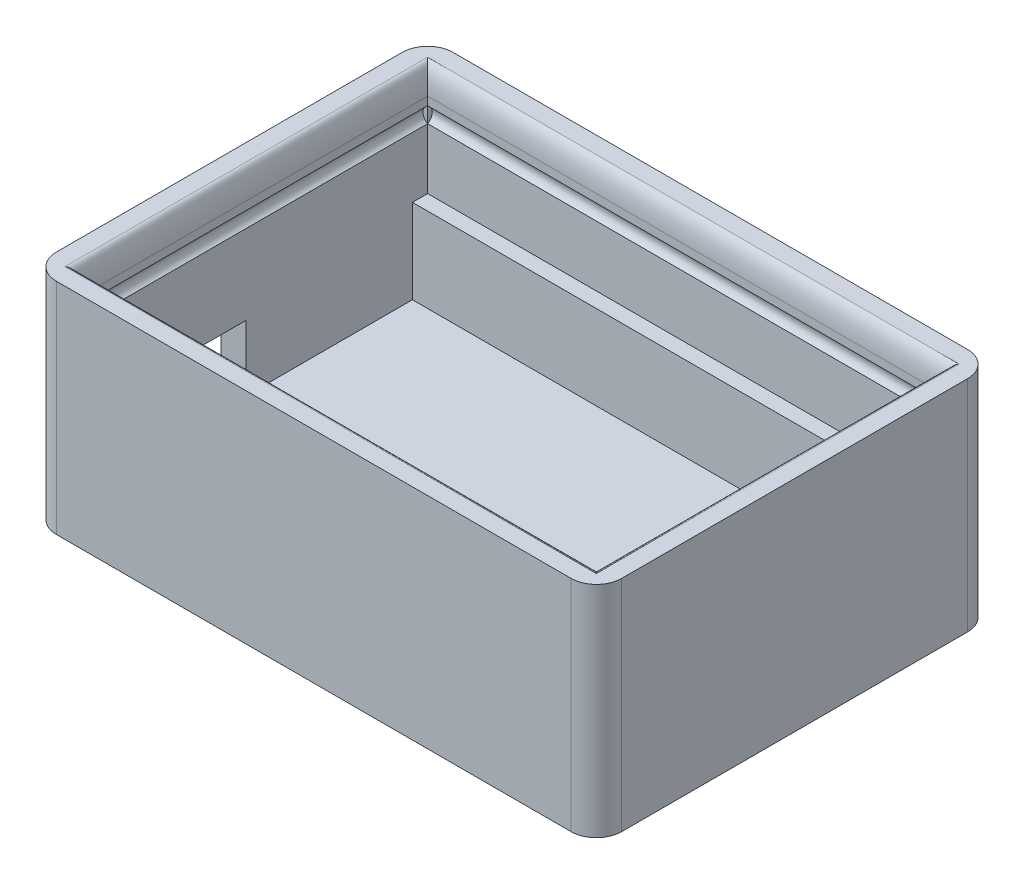
SolidWorks part; units mm, degrees
ref_plane "Front Plane" through (0, 0, 0) normal (0, 0, 1) x (1, 0, 0)
ref_plane "Top Plane" through (0, 0, 0) normal (0, 1, 0) x (1, 0, 0)
ref_plane "Right Plane" through (0, 0, 0) normal (1, 0, 0) x (0, 0, -1)
sketch "Sketch1" plane through (0, 0, 0) normal (0, 1, 0) x (1, 0, 0)
  line L1 (-30.5, 20.5) -> (30.5, 20.5)
  line L2 (-30.5, 20.5) -> (-30.5, -20.5)
  line L3 (-30.5, -20.5) -> (30.5, -20.5)
  line L4 (30.5, 20.5) -> (30.5, -20.5)
  line L5 (-30.5, 20.5) -> (30.5, -20.5) construction
  line L6 (-30.5, -20.5) -> (30.5, 20.5) construction
  point P0 (0, 0)
  dimension "D1" = 61
  dimension "D2" = 41
extrude "Boss-Extrude1" add sketch "Sketch1" along normal blind 23
shell "Shell1" thickness 3 removed face at (0, 23, 0) outward yes
sketch "Sketch2" plane through (-30.5, 0, 0) normal (1, 0, 0) x (0, 0, -1)
  line L0 (25.85, 0) -> (-25.85, 0) construction
  line L1 (-12, 7.75) -> (-1, 7.75)
  line L2 (-12, 7.75) -> (-12, 1.25)
  line L3 (-12, 1.25) -> (-1, 1.25)
  line L4 (-1, 7.75) -> (-1, 1.25)
  point P4 (-14.6792, 8.8324)
  point P5 (-14.0268, 8.9955)
  point P6 (-6.5, 1.25)
  point P8 (-12, 4.5)
  dimension "D1" = 11
  dimension "D2" = 6.5
  dimension "D3" = 6.5
  dimension "D4" = 4.5
extrude "Cut-Extrude1" cut sketch "Sketch2" against normal through all
sketch "Sketch3" plane through (0, 0, 0) normal (0, 1, 0) x (1, 0, 0)
  line L0 (30.5, -20.5) -> (30.5, 20.5) construction
  line L1 (-30.5, 20.5) -> (30.5, 20.5)
  line L2 (-30.5, 20.5) -> (-30.5, 18.7)
  line L3 (-30.5, 18.7) -> (30.5, 18.7)
  line L4 (30.5, 20.5) -> (30.5, 18.7)
  line L5 (-30.5, 20.5) -> (-30.5, -20.5) construction
  line L6 (30.5, -20.5) -> (-30.5, -20.5)
  line L7 (30.5, -20.5) -> (30.5, -18.7)
  line L8 (30.5, -18.7) -> (-30.5, -18.7)
  line L9 (-30.5, -20.5) -> (-30.5, -18.7)
  dimension "D1" = 1.8
  dimension "D2" = 1.8
extrude "Boss-Extrude2" add sketch "Sketch3" along normal blind 10
sketch "Sketch4" plane through (0, 0, -20.5) normal (0, 0, 1) x (1, 0, 0)
  line L0 (30.5, 23) -> (-30.5, 23) construction
  line L1 (-30.5, 23) -> (-30.5, 10) construction
  line L2 (0, 0) -> (0, 26.9497) construction
  circle A0 centre (-30, 18.1) radius 1.05
  circle A1 centre (30, 18.1) radius 1.05
  dimension "D1" = 2.1
  dimension "D2" = 4.9
  dimension "D3" = 0.5
extrude "Cut-Extrude2" cut sketch "Sketch4" along normal up to surface (41 mm away) up to face at (0, 16.5, 20.5)
sketch "Sketch5" plane through (-30.5, 0, 0) normal (1, 0, 0) x (0, 0, -1)
  line L0 (20.5, 23) -> (-20.5, 23) construction
  line L1 (-20.5, 23) -> (-20.5, 19.0233) construction
  line L2 (0, 0) -> (0, 16.0511) construction
  circle A0 centre (-20, 18.1) radius 1.05
  circle A1 centre (20, 18.1) radius 1.05
  dimension "D1" = 2.1
  dimension "D2" = 4.9
  dimension "D3" = 0.5
extrude "Cut-Extrude3" cut sketch "Sketch5" along normal up to surface (61 mm away) up to face at (30.5, 9.2942, 0)
fillet "Fillet1" radius 1 4 edges at (0, 23, 20.5) (30.5, 23, 0) (0, 23, -20.5) (-30.5, 23, 0) second distance 3 first distance on face at (0, 23, 0)
fillet "Fillet2" radius 3 4 edges at (33.5, 10, -23.5) (33.5, 10, 23.5) (-33.5, 10, -23.5) (-33.5, 10, 23.5)
